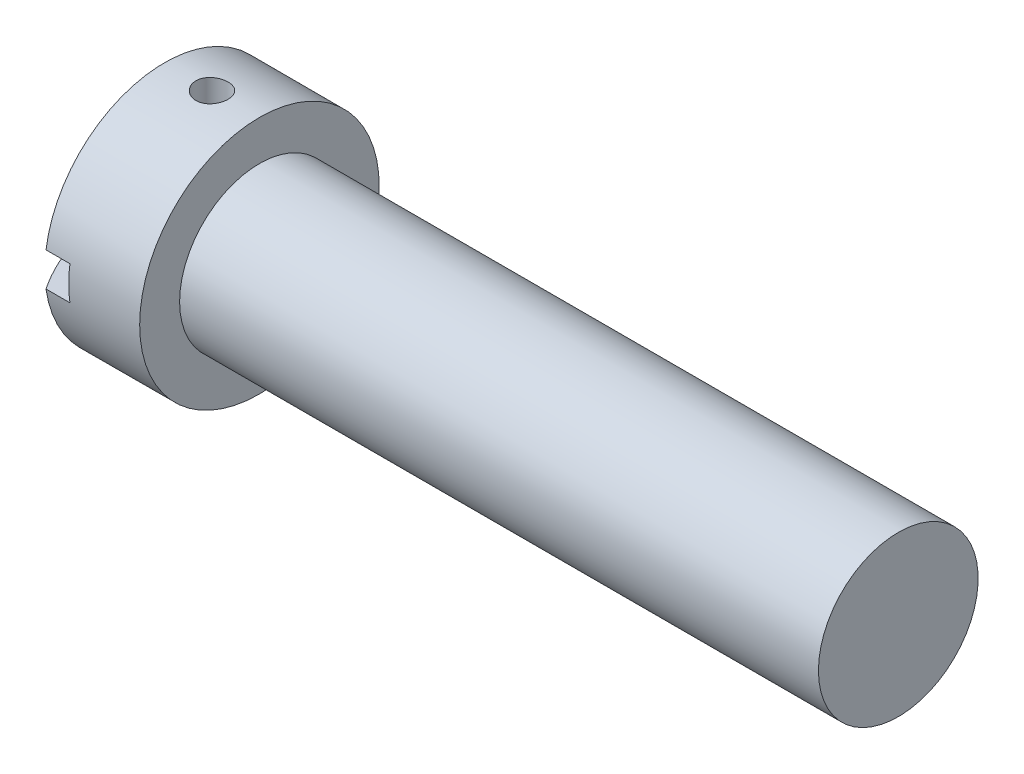
SolidWorks part; units mm, degrees
ref_plane "Plane1" through (0, 0, 0) normal (0, 0, 1) x (1, 0, 0)
ref_plane "Plane2" through (0, 0, 0) normal (0, 1, 0) x (1, 0, 0)
ref_plane "Plane3" through (0, 0, 0) normal (1, 0, 0) x (0, 0, -1)
sketch "BodySke" plane through (0, 0, 0) normal (0, 0, 1) x (1, 0, 0)
  line L0 (10.4648, 6.35) -> (10.4648, 9.525)
  line L1 (10.4648, 9.525) -> (2.921, 9.525)
  line L2 (-25.4, 0) -> (127, 0) construction
  line L3 (61.2648, 0) -> (0, 0)
  line L4 (10.4648, 6.35) -> (61.2648, 6.35)
  line L5 (61.2648, 6.35) -> (61.2648, 0)
  line L6 (10.4648, -9.525) -> (2.921, -9.525) construction
  line L7 (10.4648, -6.35) -> (61.2648, -6.35) construction
  line L8 (11.7348, 1.2192) -> (11.7348, -0.4698) construction
  line L9 (10.4648, 1.2192) -> (10.4648, -0.4698) construction
  arc A0 (0, 0) -> (2.921, 9.525) centre (16.9904, 0) cw
  dimension "Head_dia" = 19.05
  dimension "Head_ht" = 10.4648
  dimension "Length" = 50.8
  dimension "Advance" = 1.27
  dimension "Diameter" = 12.7
revolve "Base-Revolve" add sketch "BodySke" angle 360 about L2
cosmetic thread "ThreadCosmetic" [suppressed] parameters "Thread_length"=49.53, "Thread_minor"=11.1887
sketch "Sketch2" plane through (0, 0, 0) normal (1, 0, 0) x (0, 0, -1)
  line L0 (-9.525, -1.3462) -> (-9.525, 1.3462)
  line L1 (-9.525, 1.3462) -> (9.525, 1.3462)
  line L2 (9.525, 1.3462) -> (9.525, -1.3462)
  line L3 (9.525, -1.3462) -> (-9.525, -1.3462)
  dimension "D1" = 19.05
  dimension "D2" = 9.525
  dimension "D3" = 1.3462
extrude "Slot" cut sketch "Sketch2" along normal blind 4.826
sketch "Sketch3" plane through (0, 0, 0) normal (1, 0, 0) x (0, 0, -1)
  line L0 (1.1557, -7.1374) -> (-1.1557, -7.1374)
  line L1 (1.1557, -7.1374) -> (1.1557, 7.1374)
  line L2 (-1.1557, 7.1374) -> (1.1557, 7.1374)
  line L3 (-1.1557, 7.1374) -> (-1.1557, -7.1374)
  dimension "D1" = 1.1557
  dimension "D2" = 7.1374
ref_plane "Plane4" through (8.6106, 0, 0) normal (1, 0, 0) x (0, 0, -1)
sketch "Sketch4" plane through (8.6106, 0, 0) normal (1, 0, 0) x (0, 0, -1)
  line L0 (0.5778, -0.5778) -> (-0.5778, -0.5779)
  line L1 (0.5778, -0.5778) -> (0.5779, 0.5778)
  line L2 (-0.5778, 0.5778) -> (0.5779, 0.5778)
  line L3 (-0.5778, 0.5778) -> (-0.5778, -0.5779)
  dimension "D1" = 1.1557
  dimension "D2" = 0.5778
  dimension "D3" = 1.1557
  dimension "D4" = 0.5778
loft "Cross" [suppressed] cut profiles "Sketch3", "Sketch4"
pattern_circular "CirPattern1" [suppressed] count 2 every 90 about axis through (-25.4, 0, 0) along (1, 0, 0)
sketch "Sketch5" plane through (0, 0, 0) normal (0, 1, 0) x (1, 0, 0)
  line L4 (-25.4, 0) -> (127, 0) construction
  line L5 (10.4648, -6.312) -> (10.4648, 6.3337) construction
  circle A0 centre (7.2709, 0) radius 0.889
  dimension "D1" = 10.4648
extrude "Hole" [suppressed] cut sketch "Sketch5" against normal through all and the other way through all
sketch "ThdSchSke" plane through (0, 0, 0) normal (0, 0, 1) x (1, 0, 0)
  line L0 (11.7348, -5.5943) -> (11.2057, -6.35)
  line L1 (11.7348, -5.5943) -> (12.2639, -6.35)
  line L2 (12.2639, -6.35) -> (12.2639, -7.9375)
  line L3 (-3.175, 0) -> (5.1513, 0) construction
  line L5 (12.2639, -7.9375) -> (11.2057, -7.9375)
  line L6 (11.2057, -7.9375) -> (11.2057, -6.35)
  dimension "Thread_minor" = 11.1887
  dimension "Diameter" = 12.7
  dimension "Start" = 11.7348
revolve "ThreadSchematic" [suppressed] cut sketch "ThdSchSke" angle 360 about L3
pattern_linear "ThdSchPat" [suppressed]
sketch "Sketch6" plane through (0, 0, 0) normal (0, 1, 0) x (1, 0, 0)
  line L0 (2.921, 0) -> (10.4648, 0) construction
  line L1 (2.921, -9.4294) -> (2.921, 9.4294) construction
  line L2 (10.4648, -6.35) -> (10.4648, 6.35) construction
  circle A0 centre (6.6929, 0) radius 1.2789
  dimension "D1" = 2.5578
extrude "Cut-Extrude1" cut sketch "Sketch6" against normal mid plane 1271.524
equation "\"D1@Sketch3\" = \"Cross_width@Sketch3\" / 2"
equation "\"D2@Sketch3\" = \"Cross_dia@Sketch3\" / 2"
equation "\"D1@Sketch4\" = \"Cross_width@Sketch3\"*.5"
equation "\"D2@Sketch4\" = \"D1@Sketch4\" / 2"
equation "\"D3@Sketch4\" = \"D1@Sketch4\""
equation "\"D4@Sketch4\" = \"D2@Sketch4\""
equation "\"D1@Sketch2\" = \"Head_dia@BodySke\""
equation "\"D2@Sketch2\" = \"D1@Sketch2\" / 2"
equation "\"D3@Sketch2\" = \"Slot_width@Sketch2\" / 2"
equation "\"D1@Sketch5\" = \"Head_ht@BodySke\""
equation "\"Thread_length@ThreadCosmetic\" = ((sgn( (\"Length@BodySke\" - \"Advance@BodySke\" ) - \"Thread_nom@BodySke\" )-1)*( (\"Length@BodySke\" - \"Advance@BodySke\" ) - \"Thread_nom@BodySke\" ))/-2+ \"Thread_nom@BodySke\""
equation "\"Thread_minor@ThdSchSke\" = \"Thread_minor@ThreadCosmetic\""
equation "\"Diameter@ThdSchSke\" = \"Diameter@BodySke\""
equation "\"Overcut@ThdSchSke\" = \"Diameter@BodySke\" * 1.25"
equation "\"Start@ThdSchSke\" = \"Head_ht@BodySke\" + \"Length@BodySke\" - \"Thread_length@ThreadCosmetic\"  '---Non-countersunk---"
equation "\"Num_threads@ThdSchPat\" = int( \"Thread_length@ThreadCosmetic\" / \"Advance@BodySke\" + 0.999 )  + 1"
equation "\"Advance@ThdSchPat\" = \"Thread_length@ThreadCosmetic\" /  (\"Num_threads@ThdSchPat\" - 1) 'relax it"
equation "\"D1@Sketch6\" = \"Slot_width@Sketch2\"*0.95"
